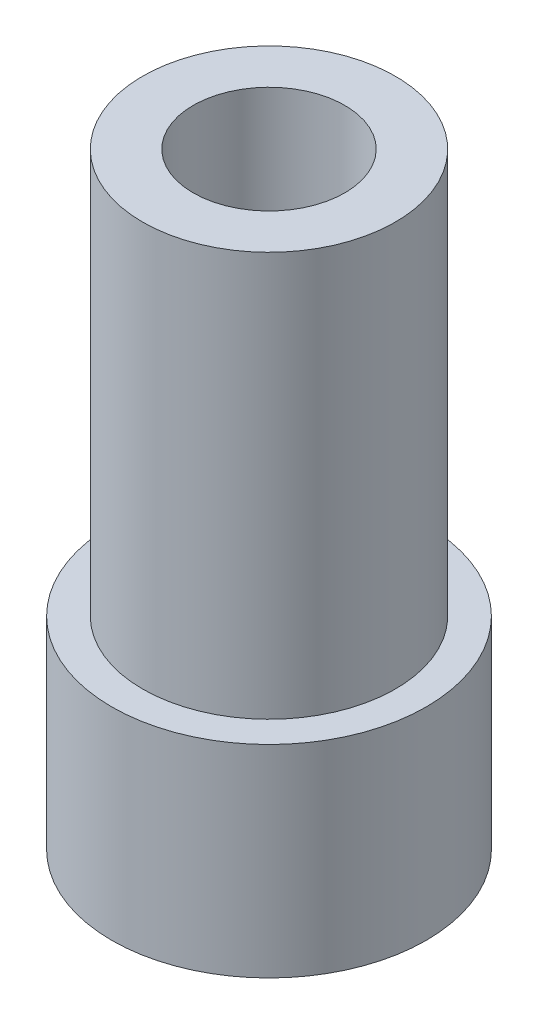
SolidWorks part; units mm, degrees
ref_plane "Plan de face" through (0, 0, 0) normal (0, 0, 1) x (1, 0, 0)
ref_plane "Plan de dessus" through (0, 0, 0) normal (0, 1, 0) x (1, 0, 0)
ref_plane "Plan de droite" through (0, 0, 0) normal (1, 0, 0) x (0, 0, -1)
sketch "Esquisse1" plane through (0, 0, 0) normal (0, 0, 1) x (1, 0, 0)
  line L0 (0, 8.6266) -> (0, -8.6266) construction
  line L1 (1.5, 4) -> (1.5, -8)
  line L2 (1.5, -8) -> (3.1111, -8)
  line L3 (3.1111, -8) -> (3.1111, -4)
  line L6 (3.1111, -4) -> (2.5, -4)
  line L7 (2.5, -4) -> (2.5, 4)
  line L12 (2.5, 4) -> (1.5, 4)
  line L13 (0, 0) -> (37.2784, 0) construction
  dimension "D1" = 8
  dimension "D2" = 5
  dimension "D3" = 3
  dimension "D4" = 6.2222
  dimension "D5" = 12
revolve "Révolution1" add sketch "Esquisse1" angle 360 about L0
